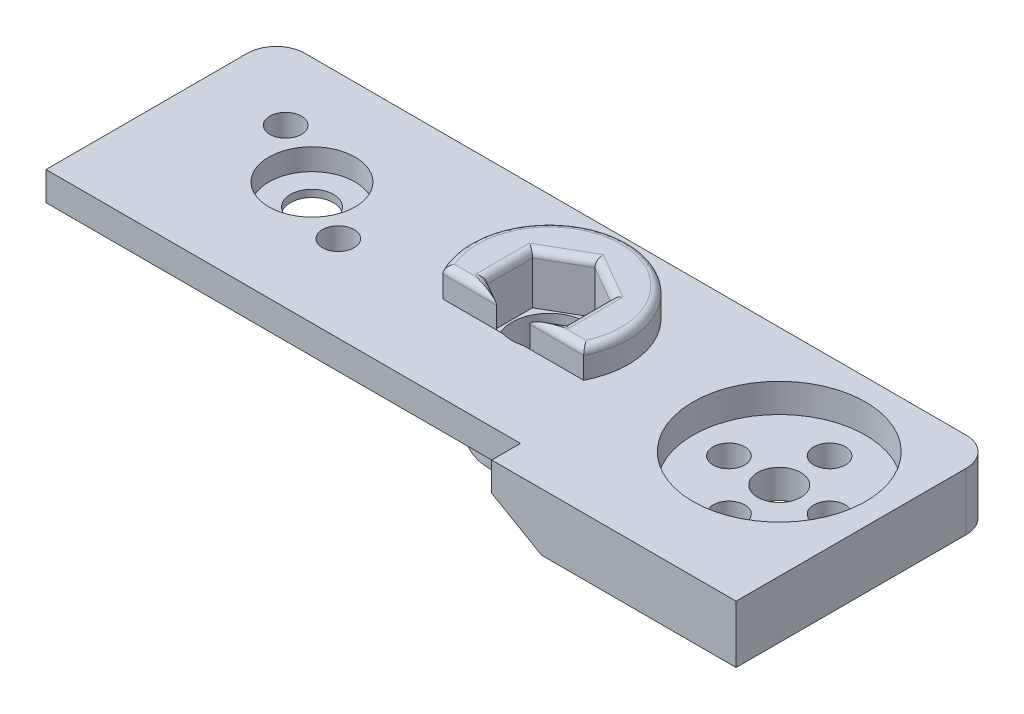
SolidWorks part; units mm, degrees
ref_plane "前视基准面" through (0, 0, 0) normal (0, 0, 1) x (1, 0, 0)
ref_plane "上视基准面" through (0, 0, 0) normal (0, 1, 0) x (1, 0, 0)
ref_plane "右视基准面" through (0, 0, 0) normal (1, 0, 0) x (0, 0, -1)
other "Configuration Table"
sketch "草图1" plane through (0, 0, 0) normal (0, 1, 0) x (1, 0, 0)
  line L0 (-25, 7.5) -> (25, 7.5)
  line L1 (25, 7.5) -> (25, -7.5)
  line L2 (25, -7.5) -> (-25, -7.5)
  line L3 (-25, -7.5) -> (-25, 7.5)
  line L4 (-25, 0) -> (25, 0) construction
  line L5 (-19.3301, -2.5) -> (-10.6699, 2.5) construction
  line L6 (-19.8083, -5.95) -> (-10.1917, -5.95) construction
  line L7 (-19.8083, 5.95) -> (-10.1917, 5.95) construction
  line L8 (-15, 7.5) -> (-15, -7.5) construction
  line L9 (1.5, 0) -> (1.5, 4.5778) construction
  line L11 (25, 7.5) -> (8, 7.5)
  line L12 (25, 7.5) -> (25, -7.5)
  line L13 (25, -7.5) -> (8, -7.5)
  line L14 (8, 7.5) -> (8, -7.5)
  circle A0 centre (-15, 0) radius 1.5
  circle A1 centre (-10.6699, 2.5) radius 1.1
  circle A3 centre (-19.3301, -2.5) radius 1.1
  arc A4 (-19.8083, 5.95) -> (-19.8083, -5.95) centre (-15, 0) ccw construction
  circle A5 centre (1.5, 0) radius 2.6
  arc A6 (-10.1917, -5.95) -> (-10.1917, 5.95) centre (-15, 0) ccw construction
  circle A7 centre (17.5, 0) radius 1.5
  circle A8 centre (17.5, 0) radius 3.5 construction
  circle A9 centre (21, 0) radius 1.1
  circle A10 centre (17.5, -3.5) radius 1.1
  circle A11 centre (14, 0) radius 1.1
  circle A12 centre (17.5, 3.5) radius 1.1
  circle A13 centre (-19.3301, 2.5) radius 1.1
  circle A14 centre (-10.6699, -2.5) radius 1.1
  circle A21 centre (17.5, 0) radius 6
  point P5 (0, 7.5)
  point P7 (-25, 0)
  dimension "D3" = 3
  dimension "D6" = 2.2
  dimension "D9" = 15.3
  dimension "D12" = 5.2
  dimension "D14" = 3
  dimension "D15" = 7
  dimension "D16" = 2.2
  dimension "D22" = 12
  dimension "D1" = 50
  dimension "D2" = 15
  dimension "D4" = 40
  dimension "D7" = 30
  dimension "D8" = 10
  dimension "D10" = 11.9
  dimension "D11" = 16.5
  dimension "D13" = 16
  dimension "D21" = 17
  dimension "D5" = 2
  dimension "D17" = 4
extrude "凸台-拉伸1" add sketch "草图1" along normal blind 2 contours A3 | L14 L0 L3 L2 A13 A3 A1 A0 A14 | L0 L14 L2 L1 A21 | A21 A7 A9 A10 A11 A12 | A5 | A1 region at (-8.6497, 0, 0) region at (16.5, 0, -7.2733) region at (-10.6699, 0, -2.5) region at (-19.3301, 0, 2.5) region at (11.6697, 0, 0)
sketch "草图4" plane through (0, 2, 0) normal (0, 1, 0) x (1, 0, 0)
  circle A0 centre (-15, 0) radius 3
  dimension "D1" = 6
extrude "切除-拉伸1" cut sketch "草图4" against normal blind 1.5
extrude "凸台-拉伸4" add sketch "草图1<3>" along normal blind 2 contours L0 L14 L2 L1 A21 | A21 A7 A9 A10 A11 A12 region at (16.5, 0, -7.2733) region at (11.6697, 0, 0)
sketch "草图1<3>" plane through (0, 0, 0) normal (0, 1, 0) x (1, 0, 0) same geometry as "草图1"
extrude "切除-拉伸4" cut sketch "草图1<5>" along normal up to surface (2 mm away) contours A21 up to face at (0, 2, 0)
sketch "草图1<5>" plane through (0, 0, 0) normal (0, 1, 0) x (1, 0, 0) same geometry as "草图1"
extrude "凸台-拉伸5" add sketch "草图1<4>" against normal blind 2 contours L0 L14 L2 L1 A21 | A21 A7 A9 A10 A11 A12 region at (16.5, 0, -7.2733) region at (11.6697, 0, 0)
sketch "草图1<4>" plane through (0, 0, 0) normal (0, 1, 0) x (1, 0, 0) same geometry as "草图1"
sketch "草图8" plane through (0, 0, -7.5) normal (0, 0, -1) x (-1, 0, 0)
  line L0 (-8, 0) -> (-11.4641, -2)
  line L1 (-8, -2) -> (-25, -2) construction
  line L2 (-11.4641, -2) -> (-8, -2)
  line L3 (-8, -2) -> (-8, 0)
  dimension "D1" = 30
extrude "切除-拉伸5" cut sketch "草图8" against normal up to surface (15 mm away) up to face at (2.6667, 0, 7.5)
sketch "草图9" plane through (0, 2, 0) normal (0, 1, 0) x (1, 0, 0)
  circle A0 centre (1.5, 0) radius 2.6
  circle A1 centre (1.5, 0) radius 5.5
  circle A2 centre (1.5, 0) radius 2.6 construction
  dimension "D1" = 11
extrude "凸台-拉伸6" add sketch "草图9" along normal blind 2
sketch "草图10" plane through (0, 4, 0) normal (0, 1, 0) x (1, 0, 0)
  line L0 (1.5, 0) -> (1.5791, 0) construction
  line L1 (1.5, 0) -> (1.5, 6.1954) construction
  line L2 (1.5, 3.1754) -> (-1.25, 1.5877)
  line L3 (-1.25, 1.5877) -> (-1.25, -1.5877)
  line L4 (1.5, 3.1754) -> (4.25, 1.5877)
  line L5 (4.25, 1.5877) -> (4.25, -1.5877)
  line L6 (1.5, -3.1754) -> (4.25, -1.5877)
  line L7 (1.5, -3.1754) -> (-1.25, -1.5877)
  line L8 (-3.399, -2.5) -> (6.399, -2.5)
  line L10 (25, -7.5) -> (-25, -7.5) construction
  circle A0 centre (1.5, 0) radius 5.5 construction
  circle A1 centre (1.5, 0) radius 5.5 construction
  arc A2 (6.399, -2.5) -> (-3.399, -2.5) centre (1.5, 0) cw
  point P11 (4.25, 0)
  point P13 (-1.25, 0)
  circle M8 centre (1.5, 0) radius 5.5
  circle M9 centre (1.5, 0) radius 2.6
  dimension "D1" = 120
  dimension "D2" = 5.5
  dimension "D3" = 5.5
  dimension "D4" = 5
extrude "切除-拉伸6" cut sketch "草图10" against normal up to surface (2 mm away) contours L8 L6 L7 M8 | L8 L7 L6 M9 region at (1.5, 4, 2.7506) region at (1.5, 4, 3.7728) up to face at (-15, 2, 3)
extrude "切除-拉伸7" cut sketch "草图10<3>" against normal blind 3.5 contours L7 L8 L6 L5 L4 L2 L3 M9 region at (2.8355, 4, -2.3131)
sketch "草图10<3>" plane through (0, 4, 0) normal (0, 1, 0) x (1, 0, 0) same geometry as "草图10"
sketch "草图13" plane through (0, 0, 7.5) normal (0, 0, 1) x (1, 0, 0)
  line L0 (8, 2) -> (8, 0)
  line L4 (8, 0) -> (8.014, -0.0373)
  line L5 (25, 2) -> (-25, 2) construction
  line L14 (8, 0) -> (11.4641, -2)
  line L16 (11.4641, -2) -> (25, -2)
  line L25 (25, -2) -> (25, 2)
  line L26 (25, 2) -> (-25, 2)
  line L27 (-25, 2) -> (-25, 0)
  line L28 (-25, 0) -> (8, 0)
  line L29 (8, 0) -> (11.4641, -2)
  line L30 (11.4641, -2) -> (25, -2)
  line L31 (25, -2) -> (25, 2)
  line L32 (25, 2) -> (8, 2)
  line M8 (11.4641, -2) -> (25, -2)
  line M10 (25, 2) -> (-25, 2)
  line M12 (-25, 0) -> (8, 0)
  line M13 (8, 0) -> (11.4641, -2)
  line M25 (25, -2) -> (25, 2)
  dimension "D1" = 0
extrude "凸台-拉伸10" add sketch "草图13" along normal blind 3 contours L0 M10 M12 M13 M8 M25 region at (16.8943, 0.0716, 7.5)
fillet "圆角1" radius 2 2 edges at (25, 0, -7.5) (-25, 1, -7.5)
sketch "草图15" plane through (0, 0, 7.5) normal (0, 0, 1) x (1, 0, 0)
  line L4 (8, 0) -> (8, 2)
  line L5 (8, 2) -> (-25, 2)
  line L6 (-25, 2) -> (-25, 0)
  line L7 (-25, 0) -> (8, 0)
  line L8 (8, 0) -> (8, 2)
  line L9 (8, 2) -> (-25, 2)
  line L10 (-25, 2) -> (-25, 0)
  line L11 (-25, 0) -> (8, 0)
  dimension "D1" = 0
extrude "凸台-拉伸12" add sketch "草图15" along normal blind 1
sketch "草图16" plane through (0, 0, 0) normal (0, -1, 0) x (1, 0, 0)
  circle A0 centre (1.5, 0) radius 2.6 construction
  circle A1 centre (1.5, 0) radius 2.6
  circle A2 centre (1.5, 0) radius 4.1
  dimension "D1" = 1.5
extrude "凸台-拉伸13" add sketch "草图16" along normal blind 5
fillet "圆角4" radius 0.5 9 edges at (1.5, 4, -5.5) (4.5344, 4, 2.5) (3.4599, 4, 2.0439) (4.25, 4, 0) (2.875, 4, -2.3816) (0.125, 4, -2.3816) (-1.25, 4, 0) (-0.4599, 4, 2.0439) (-1.5344, 4, 2.5)
